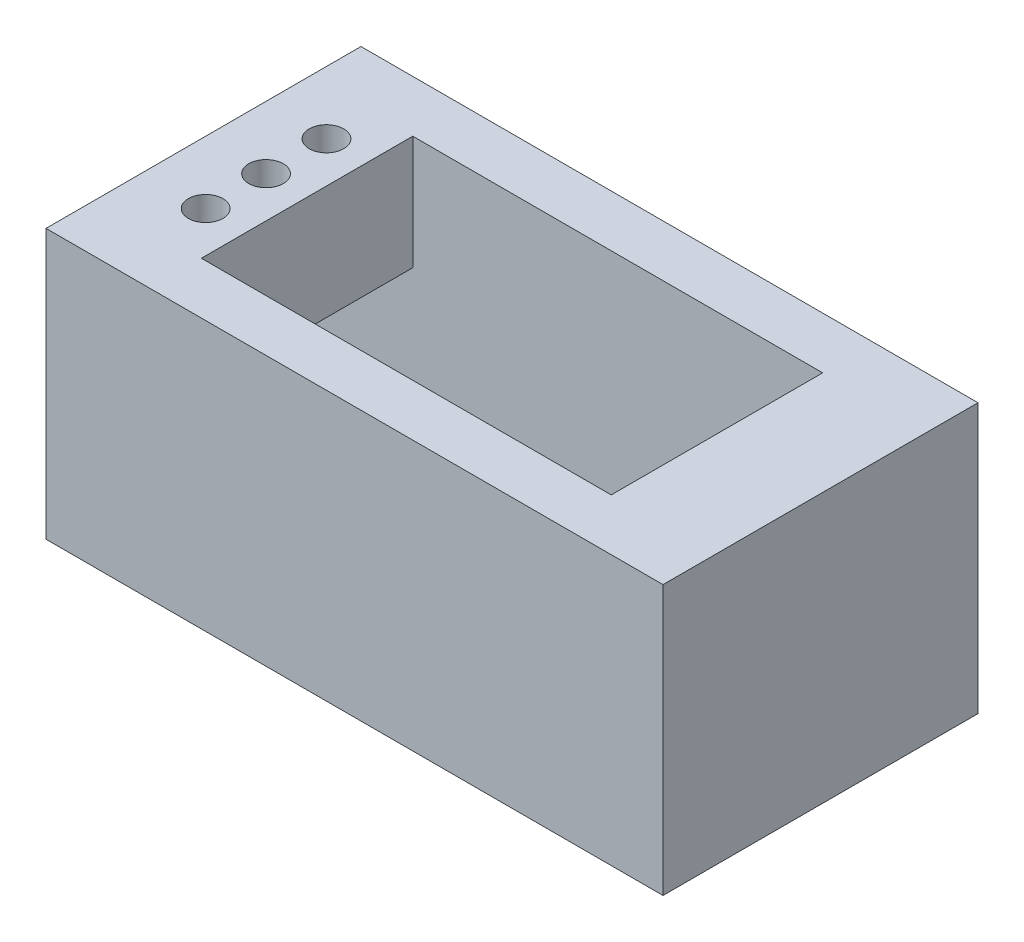
SolidWorks part; units mm, degrees
ref_plane "Front" through (0, 0, 0) normal (0, 0, 1) x (1, 0, 0)
ref_plane "Top" through (0, 0, 0) normal (0, 1, 0) x (1, 0, 0)
ref_plane "Right" through (0, 0, 0) normal (1, 0, 0) x (0, 0, -1)
sketch "Sketch1" plane through (0, 0, 0) normal (0, 1, 0) x (1, 0, 0)
  line L1 (-11.875, -6.125) -> (11.875, -6.125)
  line L2 (-11.875, -6.125) -> (-11.875, 6.125)
  line L3 (-11.875, 6.125) -> (11.875, 6.125)
  line L4 (11.875, -6.125) -> (11.875, 6.125)
  line L5 (-11.875, -6.125) -> (11.875, 6.125) construction
  line L6 (-11.875, 6.125) -> (11.875, -6.125) construction
  line L7 (-17.875, 9.125) -> (17.875, 9.125)
  line L8 (-17.875, 9.125) -> (-17.875, -9.125)
  line L9 (-17.875, -9.125) -> (17.875, -9.125)
  line L10 (17.875, 9.125) -> (17.875, -9.125)
  line L11 (-17.875, 9.125) -> (17.875, -9.125) construction
  line L12 (-17.875, -9.125) -> (17.875, 9.125) construction
  point P0 (0, 0)
  point P6 (0, 0)
  dimension "D1" = 23.75
  dimension "D2" = 12.25
  dimension "D3" = 6
  dimension "D4" = 3
extrude "Boss-Extrude1" add sketch "Sketch1" along normal blind 15.6
sketch "Sketch2" plane through (-17.875, 0, 0) normal (-1, 0, 0) x (0, 0, 1)
  line L0 (-9.125, 0) -> (9.125, 0) construction
  line L1 (-6.125, 0) -> (6.125, 0)
  line L2 (-6.125, 0) -> (-6.125, 9)
  line L3 (-6.125, 9) -> (6.125, 9)
  line L4 (6.125, 0) -> (6.125, 9)
  line L7 (6.125, 0) -> (9.125, 0)
  line L8 (-6.125, 0) -> (-9.125, 0) construction
  dimension "D1" = 9
  dimension "D4" = 12.25
extrude "Cut-Extrude1" cut sketch "Sketch2" against normal blind 10 contours L1 L2 L3 L4
sketch "Sketch3" plane through (0, 15.6, 0) normal (0, 1, 0) x (1, 0, 0)
  line L0 (17.875, 9.125) -> (-17.875, 9.125) construction
  line L1 (-17.875, 9.125) -> (-17.875, -9.125) construction
  circle A0 centre (-14.245, 3.495) radius 1
  circle A1 centre (-14.245, -0.005) radius 1
  circle A2 centre (-14.245, -3.505) radius 1
  point P6 (-12.1843, -0.3868)
  point P7 (-15.8976, -1.4699)
  point P8 (0, 0)
  dimension "D1" = 2
  dimension "D2" = 3.5
  dimension "D3" = 3.5
  dimension "D4" = 5.63
  dimension "D5" = 3.63
extrude "Cut-Extrude2" cut sketch "Sketch3" against normal blind 3
